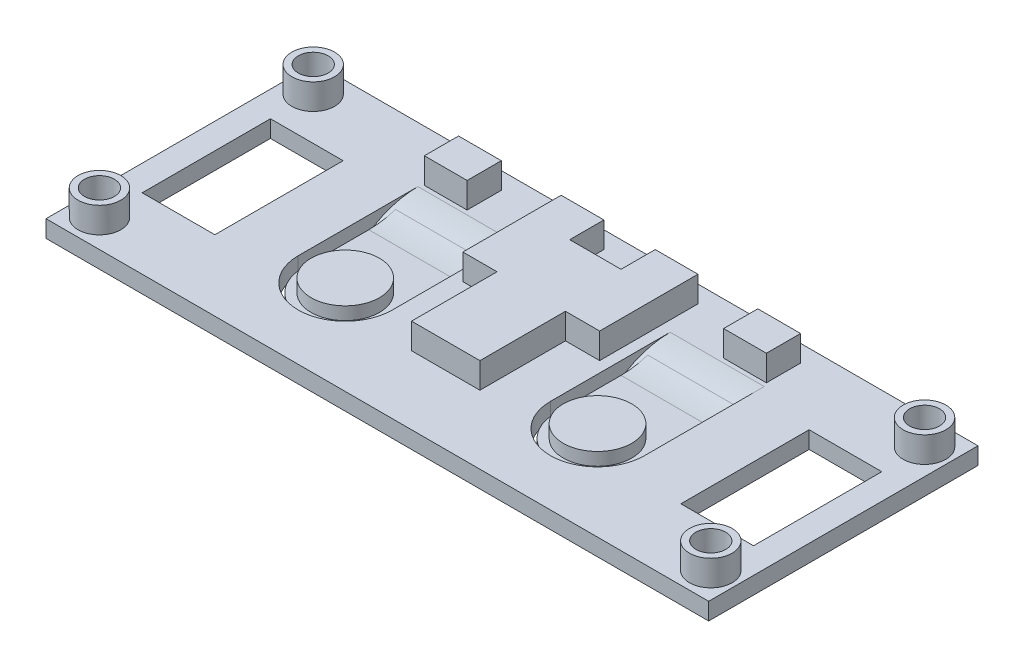
SolidWorks part; units mm, degrees
material "ABS"
ref_plane "Front Plane" through (0, 0, 0) normal (0, 0, 1) x (1, 0, 0)
ref_plane "Top Plane" through (0, 0, 0) normal (0, 1, 0) x (1, 0, 0)
ref_plane "Right Plane" through (0, 0, 0) normal (1, 0, 0) x (0, 0, -1)
sketch "Sketch1" plane through (0, 0, 0) normal (0, 1, 0) x (1, 0, 0)
  line L0 (0, 15.75) -> (0, -15.75) construction
  line L1 (-38.75, 15.75) -> (38.75, 15.75)
  line L2 (-38.75, 15.75) -> (-38.75, -15.75)
  line L3 (-38.75, -15.75) -> (38.75, -15.75)
  line L4 (38.75, 15.75) -> (38.75, -15.75)
  dimension "D1" = 77.5
  dimension "D2" = 31.5
extrude "Boss-Extrude1" add sketch "Sketch1" along normal blind 2
sketch "Sketch2" plane through (0, 2, 0) normal (0, 1, 0) x (1, 0, 0)
  line L0 (-38.75, 0) -> (39, 0) construction
  line L1 (-38.75, 15.75) -> (-38.75, -15.75) construction
  line L2 (39, -16) -> (39, 16) construction
  line L3 (0, 15.75) -> (0, -16) construction
  line L4 (38.75, 15.75) -> (-38.75, 15.75) construction
  line L5 (-39, -16) -> (39, -16) construction
  circle A0 centre (-35.75, 12.5) radius 1.75
  circle A1 centre (-35.75, -12.5) radius 1.75
  circle A2 centre (35.75, -12.5) radius 1.75
  circle A3 centre (35.75, 12.5) radius 1.75
  dimension "D1" = 3.5
extrude "Cut-Extrude1" cut sketch "Sketch2" against normal through all both and the other way through all
sketch "Sketch3" plane through (0, 2, 0) normal (0, 1, 0) x (1, 0, 0)
  line L0 (0, 15.75) -> (0, -15.75) construction
  line L1 (38.75, 15.75) -> (-38.75, 15.75) construction
  line L2 (-38.75, -15.75) -> (38.75, -15.75) construction
  line L3 (-38.75, 0) -> (38.75, 0) construction
  line L4 (27.25, 7.5) -> (35.75, 7.5)
  line L5 (27.25, 7.5) -> (27.25, -7.5)
  line L6 (27.25, -7.5) -> (35.75, -7.5)
  line L7 (35.75, 7.5) -> (35.75, -7.5)
  line L8 (-38.75, 15.75) -> (-38.75, -15.75) construction
  line L9 (38.75, -15.75) -> (38.75, 15.75) construction
  line L10 (31.5, 7.5) -> (31.5, -7.5) construction
  line L11 (-31.5, 7.5) -> (-31.5, -7.5) construction
  line L12 (-35.75, 7.5) -> (-35.75, -7.5)
  line L13 (-27.25, -7.5) -> (-35.75, -7.5)
  line L14 (-27.25, 7.5) -> (-27.25, -7.5)
  line L15 (-27.25, 7.5) -> (-35.75, 7.5)
  point P18 (31.5, 0)
  dimension "D1" = 8.5
  dimension "D2" = 15
  dimension "D3" = 27.25
extrude "Cut-Extrude2" cut sketch "Sketch3" against normal through all both and the other way through all
sketch "Sketch4" plane through (0, 2, 0) normal (0, 1, 0) x (1, 0, 0)
  circle A1 centre (-35.75, 12.5) radius 1.75 construction
  circle A2 centre (-35.75, 12.5) radius 2.5
  circle A3 centre (-35.75, 12.5) radius 2.5
  circle A4 centre (-35.75, 12.5) radius 1.75
  dimension "D1" = 0.75
extrude "Boss-Extrude2" add sketch "Sketch4" along normal blind 3
mirror "Mirror1" about plane through (0, 0, 0) normal (0, 0, 1) of "Boss-Extrude2"
mirror "Mirror2" about plane through (0, 0, 0) normal (1, 0, 0) of "Mirror1", "Boss-Extrude2"
sketch "Sketch5" plane through (0, 2, 0) normal (0, 1, 0) x (1, 0, 0)
  line L0 (0, 15.75) -> (0, -15.75) construction
  line L1 (38.75, 15.75) -> (-38.75, 15.75) construction
  line L2 (-38.75, -15.75) -> (38.75, -15.75) construction
  line L3 (14.75, -15.75) -> (14.75, 15.75) construction
  line L4 (38.75, -15.75) -> (38.75, 15.75) construction
  line L5 (19.75, -4.75) -> (19.75, 3.25)
  line L6 (9.75, -4.75) -> (9.75, 3.25)
  line L7 (9.75, 3.25) -> (19.75, 3.25) construction
  line L8 (9.25, -4.75) -> (9.25, 3.25)
  line L9 (20.25, -4.75) -> (20.25, 3.25)
  line L10 (9.25, 3.25) -> (9.75, 3.25)
  line L11 (19.75, 3.25) -> (20.25, 3.25)
  line L12 (-9.75, 3.25) -> (-19.75, 3.25) construction
  line L13 (-19.75, 3.25) -> (-20.25, 3.25)
  line L14 (-9.25, 3.25) -> (-9.75, 3.25)
  line L15 (-20.25, -4.75) -> (-20.25, 3.25)
  line L16 (-9.25, -4.75) -> (-9.25, 3.25)
  line L17 (-9.75, -4.75) -> (-9.75, 3.25)
  line L18 (-19.75, -4.75) -> (-19.75, 3.25)
  arc A0 (9.75, -4.75) -> (19.75, -4.75) centre (14.75, -4.75) ccw
  arc A1 (9.25, -4.75) -> (20.25, -4.75) centre (14.75, -4.75) ccw
  arc A2 (-9.25, -4.75) -> (-20.25, -4.75) centre (-14.75, -4.75) cw
  arc A3 (-9.75, -4.75) -> (-19.75, -4.75) centre (-14.75, -4.75) cw
  dimension "D2" = 10
  dimension "D1" = 24
  dimension "D3" = 11
  dimension "D4" = 8
  dimension "D5" = 0.5
extrude "Cut-Extrude3" cut sketch "Sketch5" against normal blind 3.5
sketch "Sketch6" plane through (0, 2, 0) normal (0, 1, 0) x (1, 0, 0)
  line L0 (0, 2.25) -> (0, -7.75) construction
  line L1 (-4, 2.25) -> (4, 2.25)
  line L2 (-4, 2.25) -> (-4, -7.75)
  line L3 (-4, -7.75) -> (4, -7.75)
  line L4 (4, 2.25) -> (4, -7.75)
  line L5 (5.5, 15.75) -> (5.5, -15.75) construction
  line L6 (38.75, 15.75) -> (-38.75, 15.75) construction
  line L7 (-38.75, -15.75) -> (38.75, -15.75) construction
  line L8 (3, 11.75) -> (8, 11.75) construction
  line L9 (3, 13.75) -> (8, 13.75)
  line L10 (3, 13.75) -> (3, 9.75)
  line L11 (3, 9.75) -> (8, 9.75)
  line L12 (8, 13.75) -> (8, 9.75)
  line L13 (11.5, -15.75) -> (11.5, 15.75) construction
  line L14 (20, 9.75) -> (15, 9.75)
  line L15 (20, 13.75) -> (20, 9.75)
  line L16 (20, 13.75) -> (15, 13.75)
  line L17 (15, 13.75) -> (15, 9.75)
  line L18 (-11.5, -15.75) -> (-11.5, 15.75) construction
  line L19 (-3, 11.75) -> (-8, 11.75) construction
  line L20 (-5.5, 15.75) -> (-5.5, -15.75) construction
  line L21 (-15, 13.75) -> (-15, 9.75)
  line L22 (-20, 13.75) -> (-15, 13.75)
  line L23 (-20, 13.75) -> (-20, 9.75)
  line L24 (-20, 9.75) -> (-15, 9.75)
  line L25 (-8, 13.75) -> (-8, 9.75)
  line L26 (-3, 9.75) -> (-8, 9.75)
  line L27 (-3, 13.75) -> (-3, 9.75)
  line L28 (-3, 13.75) -> (-8, 13.75)
  point P19 (5.5, 11.75)
  point P40 (4, 2.6925)
  point P42 (10, 3.5397)
  point P43 (0, 0)
  dimension "D1" = 8
  dimension "D2" = 8
  dimension "D3" = 5
  dimension "D4" = 2
  dimension "D5" = 4
  dimension "D6" = 3
  dimension "D7" = 6
  dimension "D8" = 10
extrude "Boss-Extrude3" add sketch "Sketch6" along normal up to surface (3 mm away) up to face at (-35.75, 5, -10)
sketch "Sketch7" plane through (0, 2, 0) normal (0, 1, 0) x (1, 0, 0)
  line L0 (8, 9.75) -> (8, 13.75) construction
  line L1 (-8, 9.75) -> (8, 9.75)
  line L2 (-8, 9.75) -> (-8, 2.25)
  line L3 (-8, 2.25) -> (8, 2.25)
  line L4 (8, 9.75) -> (8, 2.25)
  line L5 (4, 2.25) -> (-4, 2.25) construction
extrude "Boss-Extrude4" add sketch "Sketch7" along normal up to surface (3 mm away) up to face at (0, 5, 2.75)
sketch "Sketch8" plane through (0, 2, 0) normal (0, 1, 0) x (1, 0, 0)
  line L0 (-9.75, 3.25) -> (-9.75, -4.75) construction
  line L1 (-19.75, -4.75) -> (-19.75, 3.25) construction
  line L2 (-9.75, 3.25) -> (-9.75, -4.75)
  line L3 (-19.75, -4.75) -> (-19.75, 3.25)
  line L4 (-19.75, 3.25) -> (-9.75, 3.25)
  line L5 (0, -16.3364) -> (0, 15.75) construction
  line L6 (38.75, 15.75) -> (-38.75, 15.75) construction
  line L7 (19.75, 3.25) -> (9.75, 3.25)
  line L8 (19.75, -4.75) -> (19.75, 3.25)
  line L9 (9.75, 3.25) -> (9.75, -4.75)
  arc A0 (-19.75, -4.75) -> (-9.75, -4.75) centre (-14.75, -4.75) ccw construction
  arc A1 (-19.75, -4.75) -> (-9.75, -4.75) centre (-14.75, -4.75) ccw
  arc A2 (19.75, -4.75) -> (9.75, -4.75) centre (14.75, -4.75) cw
extrude "Cut-Extrude4" cut sketch "Sketch8" against normal blind 1
fillet "Fillet1" radius 10 2 edges at (14.75, 2, -3.25) (-14.75, 2, -3.25)
fillet "Fillet2" radius 10 2 edges at (-14.75, 1, -4.8911) (14.75, 1, -4.8911)
sketch "Sketch9" plane through (0, 1, 0) normal (0, 1, 0) x (1, 0, 0)
  line L0 (0, 16.0456) -> (0, -23.9554) construction
  circle A0 centre (14.75, -4.75) radius 4
  arc A1 (9.75, -4.75) -> (19.75, -4.75) centre (14.75, -4.75) ccw construction
  circle A2 centre (-14.75, -4.75) radius 4
  dimension "D1" = 8
extrude "Boss-Extrude6" add sketch "Sketch9" along normal blind 1.5
sketch "Sketch11" plane through (0, 0, 0) normal (0, -1, 0) x (1, 0, 0)
  line L0 (26.75, -5) -> (20.0794, -5) construction
  line L1 (26.75, -15.75) -> (26.75, 15.75) construction
  line L2 (38.75, -15.75) -> (-38.75, -15.75) construction
  line L3 (-38.75, 15.75) -> (38.75, 15.75) construction
  line L4 (4.8973, 0) -> (-5.0855, 0) construction
  line L5 (27.25, -7.5) -> (27.25, 7.5) construction
  line L6 (35.75, -7.5) -> (27.25, -7.5) construction
  text T0 "RECORD" font "Century Gothic" height 1
  dimension "D1" = 0.5
  dimension "D2" = 2.5
